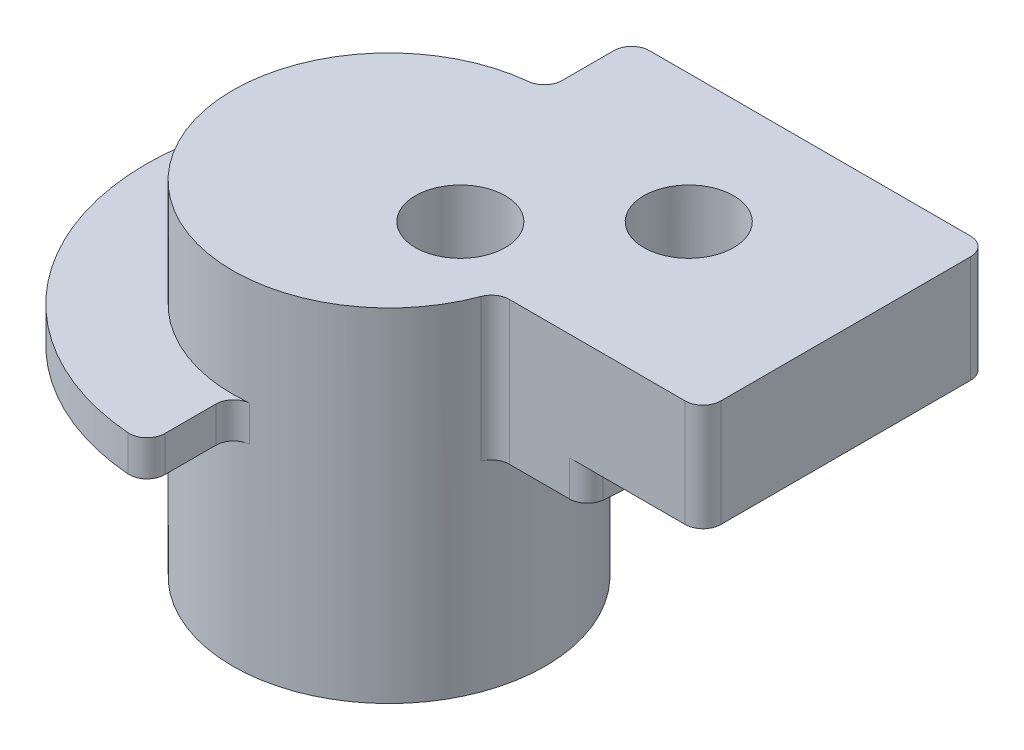
SolidWorks part; units mm, degrees
material "PET"
ref_plane "Front Plane" through (0, 0, 0) normal (1, 0, 0) x (0, 1, 0)
ref_plane "Top Plane" through (0, 0, 0) normal (0, 0, 1) x (0, 1, 0)
ref_plane "Right Plane" through (0, 0, 0) normal (0, 1, 0) x (-1, 0, 0)
sketch "Sketch2" plane through (0, 0, 0) normal (0, 0, 1) x (0, 1, 0)
  line L0 (0, 6.95) -> (0, -6.95) construction
  line L1 (15.24, -6.95) -> (-15.24, -6.95)
  line L2 (15.24, -6.95) -> (15.24, 6.95)
  line L3 (15.24, 6.95) -> (-15.24, 6.95)
  line L4 (-15.24, -6.95) -> (-15.24, 6.95)
  line L5 (15.24, -6.95) -> (-15.24, 6.95) construction
  line L6 (15.24, 6.95) -> (-15.24, -6.95) construction
  line L11 (-10.4775, 10.795) -> (-8.89, 10.795)
  line L12 (-10.4775, 10.795) -> (-10.4775, -10.795)
  line L19 (-10.4775, -10.795) -> (-8.89, -10.795)
  line L20 (-8.89, 10.795) -> (-8.89, -10.795)
  line L21 (10.4775, -10.795) -> (8.89, -10.795)
  line L22 (8.89, 10.795) -> (8.89, -10.795)
  line L23 (10.4775, 10.795) -> (8.89, 10.795)
  line L24 (10.4775, 10.795) -> (10.4775, -10.795)
  line L25 (-15.24, 0) -> (15.24, 0)
  point P0 (0, 0)
  point P6 (0, 0)
  point P11 (0, 0)
  point P16 (-10.4775, 0)
  dimension "D1" = 13.9
  dimension "D2" = 30.48
  dimension "D5" = 1.5875
  dimension "D6" = 21.59
  dimension "D7" = 8.89
revolve "Revolve2" add sketch "Sketch2" angle 360 about L25 region at (-3.475, 12.8588, 0) region at (-3.475, 9.6838, 0) region at (-3.475, 0, 0) region at (-8.8725, 9.6838, 0) region at (-3.475, -9.6838, 0) region at (-3.475, -12.8588, 0) region at (-8.8725, -9.6838, 0)
sketch "Sketch3" plane through (0, 0, 0) normal (0, 1, 0) x (-1, 0, 0)
  circle A0 centre (0, 0) radius 11.3381
extrude "Cut-Extrude1" cut sketch "Sketch3" against normal blind 21.336
sketch "Sketch5" plane through (0, 15.24, 0) normal (0, 1, 0) x (-1, 0, 0)
  line L5 (0, -10.795) -> (-15.875, -10.795)
  line L6 (0, -10.795) -> (0, 1.905)
  line L7 (0, 1.905) -> (-15.875, 1.905)
  line L8 (-15.875, -10.795) -> (-15.875, 1.905)
  circle A0 centre (-3.175, 0) radius 2
  circle A1 centre (0, 0) radius 6.95 construction
  circle A2 centre (0, 0) radius 6.95 construction
  circle A3 centre (-3.175, 0) radius 3.6 construction
  circle A9 centre (0, 0) radius 6.95
  circle A10 centre (-8.255, -5.08) radius 2
  circle A13 centre (0, 0) radius 10.795 construction
  circle A14 centre (-8.255, -5.08) radius 3.6 construction
  circle A15 centre (0, 0) radius 10.541 construction
  point P4 (6.95, 0)
  point P13 (-3.175, 2)
  point P15 (-3.175, 3.6)
  point P20 (-6.255, -5.08)
  point P21 (-4.655, -5.08)
  circle M7 centre (0, 0) radius 6.95
  dimension "D8" = 1.6
  dimension "D3" = 4
  dimension "D7" = 15.875
  dimension "D10" = 21.082
  dimension "D2" = 3.175
  dimension "D4" = 5.08
  dimension "D5" = 1.6
  dimension "D6" = 12.7
  dimension "D9" = 5.08
  dimension "5" = 0
extrude "Cut-Extrude3" cut sketch "Sketch5" against normal blind 27.432 contours A0 | L7 A0 region at (3.175, 15.24, -0.0121) region at (3.175, 15.24, 1.9431)
extrude "Boss-Extrude2" add sketch "Sketch5<3>" against normal up to surface (4.7625 mm away) contours L8 A10 M7 region at (7.9375, 15.24, -10.5917) up to face at (6.95, 10.4775, 0)
sketch "Sketch5<3>" plane through (0, 15.24, 0) normal (0, 1, 0) x (-1, 0, 0) same geometry as "Sketch5"
fillet "Fillet1" radius 0.7937 5 edges at (0, 12.8588, -10.795) (0, 12.8588, -6.95) (15.875, 12.8588, -10.795) (6.6838, 12.8588, 1.905) (15.875, 12.8588, 1.905)
sketch "Sketch6" plane through (0, 10.4775, 0) normal (0, 1, 0) x (-1, 0, 0)
  line L0 (0, 6.95) -> (0, 10.795)
  line L3 (0, -7.703) -> (0, -10.0013)
  line L4 (-10.6256, 1.905) -> (-7.2583, 1.905)
  line L5 (0, -7.703) -> (0, -10.0013)
  line L6 (-10.6256, 1.905) -> (-7.2583, 1.905)
  arc A0 (0.7124, -6.9134) -> (-6.5143, 2.4221) centre (0, 0) ccw construction
  arc A1 (-0.6251, -10.7769) -> (-10.6256, 1.905) centre (0, 0) ccw construction
  arc A7 (0.7124, -6.9134) -> (-6.5143, 2.4221) centre (0, 0) ccw
  arc A8 (0.7124, -6.9134) -> (0, -7.703) centre (0.7938, -7.703) ccw
  arc A9 (-0.6251, -10.7769) -> (0, -10.0013) centre (-0.7937, -10.0013) ccw
  arc A10 (-0.6251, -10.7769) -> (-10.6256, 1.905) centre (0, 0) ccw
  arc A11 (-7.2583, 1.905) -> (-6.5143, 2.4221) centre (-7.2583, 2.6987) ccw
  arc A12 (0.7124, -6.9134) -> (-6.5143, 2.4221) centre (0, 0) ccw
  arc A13 (0.7124, -6.9134) -> (0, -7.703) centre (0.7938, -7.703) ccw
  arc A14 (-0.6251, -10.7769) -> (0, -10.0013) centre (-0.7937, -10.0013) ccw
  arc A15 (-0.6251, -10.7769) -> (-10.6256, 1.905) centre (0, 0) ccw
  arc A16 (-7.2583, 1.905) -> (-6.5143, 2.4221) centre (-7.2583, 2.6987) ccw
  arc M8 (-6.5143, 2.4221) -> (0.7124, -6.9134) centre (0, 0) cw
  arc M12 (-0.6251, -10.7769) -> (-10.6256, 1.905) centre (0, 0) ccw
  line M13 (-10.6256, 1.905) -> (-7.2583, 1.905)
  arc M14 (-7.2583, 1.905) -> (-6.5143, 2.4221) centre (-7.2583, 2.6987) ccw
  dimension "D1" = 0
extrude "Cut-Extrude4" cut sketch "Sketch6" against normal blind 14.224 contours L0 M8 M12 M13 M14 region at (5.2452, 10.4775, 6.5067)
fillet "Fillet2" radius 0.7937 3 edges at (10.6256, 9.6838, 1.905) (0, 9.6838, 6.95) (0, 9.6838, 10.795)
